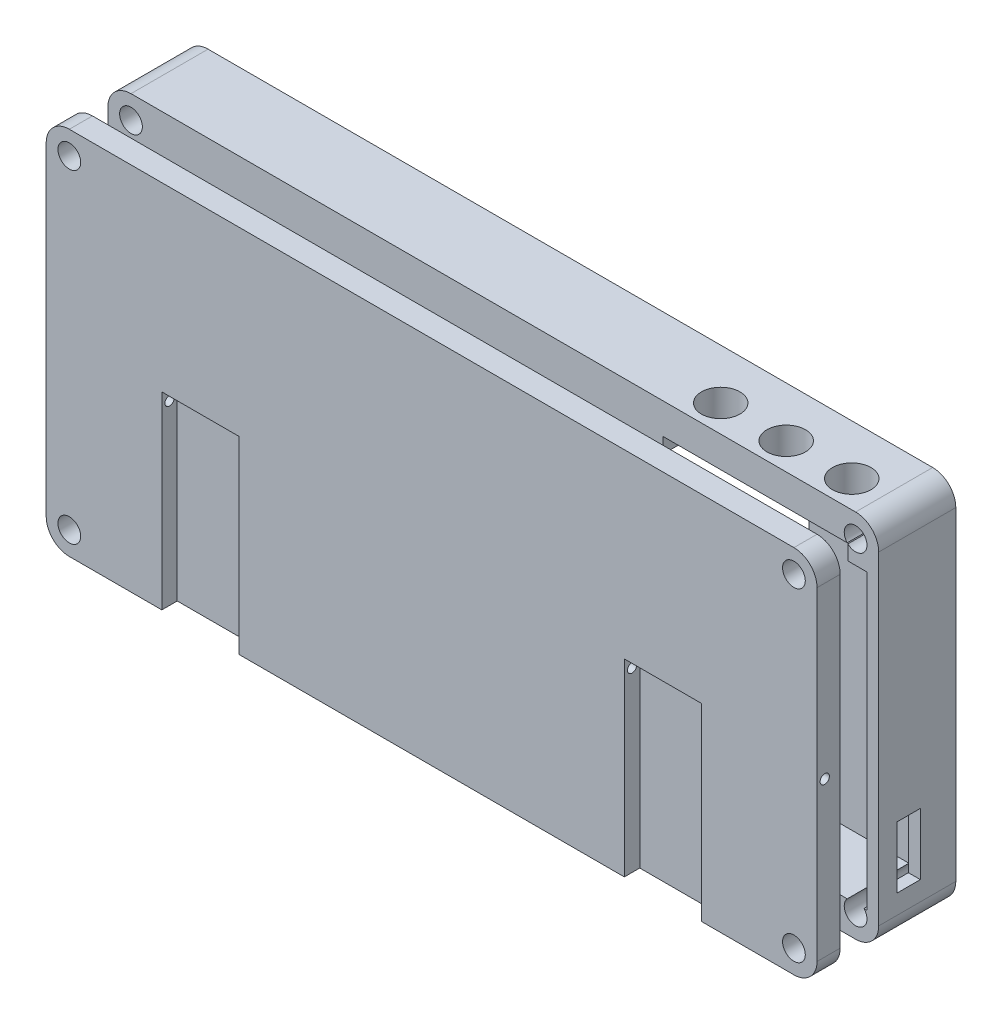
SolidWorks part; units mm, degrees
ref_plane "前视" through (0, 0, 0) normal (0, 0, 1) x (1, 0, 0)
ref_plane "上视" through (0, 0, 0) normal (0, 1, 0) x (1, 0, 0)
ref_plane "右视" through (0, 0, 0) normal (1, 0, 0) x (0, 0, -1)
sketch "草图1" plane through (0, 0, 0) normal (1, 0, 0) x (0, 0, -1)
  line L0 (0, 0) -> (10, 0)
  line L1 (0, 48) -> (0, 0)
  line L2 (10, 0) -> (10, 48)
  line L3 (10, 48) -> (0, 48)
  dimension "D1" = 10
  dimension "D2" = 48
extrude "凸台-拉伸2" add sketch "草图1" along normal blind 100 contours L1 L0 L2 L3
sketch "草图4" plane through (0, 0, 0) normal (0, 0, 1) x (1, 0, 0)
  line L0 (50, 0) -> (50, 46) construction
  line L1 (100, 0) -> (0, 0) construction
  line L2 (100, 48) -> (0, 48) construction
  line L3 (100, 48) -> (100, 0) construction
  line L4 (1.55, 42) -> (98.45, 42)
  line L5 (1.55, 42) -> (1.55, 4)
  line L6 (1.55, 4) -> (98.45, 4)
  line L7 (98.45, 42) -> (98.45, 4)
  line L8 (1.55, 42) -> (98.45, 4) construction
  line L9 (1.55, 4) -> (98.45, 42) construction
  line L10 (81.945, 37.525) -> (82.945, 36.525)
  line L11 (18.055, 37.525) -> (81.945, 37.525)
  line L12 (17.055, 36.525) -> (17.055, 10.475)
  line L13 (18.055, 9.475) -> (81.945, 9.475)
  line L14 (82.945, 36.525) -> (82.945, 10.475)
  line L15 (17.055, 37.525) -> (82.945, 9.475) construction
  line L16 (17.055, 9.475) -> (82.945, 37.525) construction
  line L17 (17.055, 36.525) -> (18.055, 37.525)
  line L18 (17.055, 10.475) -> (18.055, 9.475)
  line L19 (81.945, 9.475) -> (82.945, 10.475)
  point P6 (50, 23)
  point P13 (50, 23.5)
  dimension "D2" = 38
  dimension "D3" = 96.9
  dimension "D4" = 1.55
  dimension "D6" = 65.89
  dimension "D7" = 28.05
  dimension "D8" = 2
extrude "切除-拉伸3" cut sketch "草图4" against normal through all contours L14 L11 L12 L13 region at (50, 23.5, 0)
extrude "切除-拉伸4" cut sketch "草图4<3>" against normal offset from surface (8 mm away) 2 contours L7 L4 L5 L6 L11 L14 L13 L12 region at (50, 40.9592, 0) up to face at (50, 23.5, -10)
sketch "草图4<3>" plane through (0, 0, 0) normal (0, 0, 1) x (1, 0, 0) same geometry as "草图4"
chamfer "倒角4" distance 2 angle 60 8 edges at (17.055, 23.5, -10) (17.555, 37.025, -10) (50, 37.525, -10) (82.445, 37.025, -10) (82.945, 23.5, -10) (82.445, 9.975, -10) (50, 9.475, -10) (17.555, 9.975, -10) first distance on face at (17.055, 23.5, -9) first distance on face at (17.555, 37.025, -9) first distance on face at (50, 37.525, -9) first distance on face at (82.445, 37.025, -9) first distance on face at (82.945, 23.5, -9) first distance on face at (82.445, 9.975, -9) first distance on face at (50, 9.475, -9) first distance on face at (17.555, 9.975, -9)
fillet "圆角1" radius 3 4 edges at (0, 0, -5) (100, 0, -5) (0, 48, -5) (100, 48, -5)
sketch "草图13" plane through (0, 0, 0) normal (0, 0, 1) x (1, 0, 0)
  line L0 (1.55, 42) -> (98.45, 42) construction
  line L1 (96, 42) -> (72, 42)
  line L2 (96, 42) -> (96, 44)
  line L3 (96, 44) -> (72, 44)
  line L4 (72, 42) -> (72, 44)
  line L5 (100, 45) -> (100, 3) construction
  dimension "D1" = 4
  dimension "D2" = 28
  dimension "D3" = 2
extrude "切除-拉伸17" cut sketch "草图13" against normal up to surface (8 mm away) up to face at (50, 23, -8)
sketch "草图12" plane through (0, 48, 0) normal (0, 1, 0) x (1, 0, 0)
  line L1 (97, 10) -> (3, 10) construction
  line L3 (93, 3.5) -> (58.4452, 3.5) construction
  line L9 (100, 10) -> (100, 0) construction
  circle A0 centre (76, 3.5) radius 2.5
  circle A1 centre (93, 3.5) radius 2.5
  circle A2 centre (84.5, 3.5) radius 2.5
  dimension "D1" = 5
  dimension "D2" = 24
  dimension "D6" = 7
  dimension "D4" = 5
  dimension "D5" = 5
  dimension "D7" = 15.5
  dimension "D8" = 6.5
extrude "切除-拉伸18" cut sketch "草图12" against normal up to next contours A1 | L3 A2 | A2 L3 | L3 A0 | A0 L3 region at (76, 48, -2.439) region at (76, 48, -4.561) region at (84.5, 48, -2.439) region at (84.5, 48, -4.561) region at (93, 48, -5.9293)
sketch "草图15" plane through (0, 0, 0) normal (0, -1, 0) x (1, 0, 0)
  line L1 (68.5, -7) -> (72.5, -7)
  line L2 (68.5, -7) -> (68.5, -3)
  line L3 (68.5, -3) -> (72.5, -3)
  line L4 (72.5, -7) -> (72.5, -3)
  line L5 (100, 0) -> (100, -10) construction
  line L6 (97, -5) -> (89.4882, -5) construction
  line L7 (97, -10) -> (97, 0) construction
  arc A0 (68.5, -3) -> (68.5, -7) centre (68.5, -5) ccw
  arc A1 (72.5, -3) -> (72.5, -7) centre (72.5, -5) cw
  dimension "D1" = 27.5
  dimension "D2" = 31.5
  dimension "D3" = 4
sketch "草图14" plane through (100, 0, 0) normal (1, 0, 0) x (0, 0, -1)
  line L0 (10, 0) -> (0, 0) construction
  line L1 (2.4, 5.5) -> (5.4, 5.5)
  line L2 (2.4, 5.5) -> (2.4, 13.5)
  line L3 (2.4, 13.5) -> (5.4, 13.5)
  line L4 (5.4, 5.5) -> (5.4, 13.5)
  line L5 (8, 4) -> (8, 42) construction
  point P6 (3.9, 5.5)
  point P9 (8, 23)
  dimension "D1" = 8
  dimension "D2" = 3
  dimension "D3" = 5.5
  dimension "D4" = 2.6
extrude "切除-拉伸19" cut sketch "草图14" against normal up to next
extrude "切除-拉伸20" cut sketch "草图15" against normal up to next contours L1 L4 L3 L2 | A1 L4 | L2 A0 region at (70.5, 0, -5) region at (67.6512, 0, -5) region at (73.3488, 0, -5)
sketch "草图16" plane through (0, 0, 0) normal (0, 0, 1) x (1, 0, 0)
  line L0 (1.55, 4) -> (98.45, 4) construction
  line L1 (63.5, 4) -> (77.5, 4)
  line L2 (63.5, 4) -> (63.5, 2)
  line L3 (63.5, 2) -> (77.5, 2)
  line L4 (77.5, 4) -> (77.5, 2)
  line L8 (74.5, 0) -> (74.5, 4) construction
  line L9 (66.5, 4) -> (66.5, 0) construction
  dimension "D1" = 2
  dimension "D2" = 3
  dimension "D3" = 3
extrude "切除-拉伸21" cut sketch "草图16" against normal up to surface (8 mm away) up to face at (67, 33, -8)
sketch "草图7" plane through (0, 0, 0) normal (0, 0, 1) x (1, 0, 0)
  line L4 (0, 45) -> (0, 3)
  line L5 (3, 0) -> (97, 0)
  line L6 (3, 0) -> (97, 0)
  line L7 (100, 3) -> (100, 45)
  line L8 (0, 45) -> (0, 3)
  line L9 (100, 3) -> (100, 45)
  line L10 (97, 48) -> (3, 48)
  line L11 (97, 48) -> (3, 48)
  arc A4 (0, 3) -> (3, 0) centre (3, 3) ccw
  arc A5 (97, 0) -> (100, 3) centre (97, 3) ccw
  arc A6 (97, 0) -> (100, 3) centre (97, 3) ccw
  arc A7 (3, 48) -> (0, 45) centre (3, 45) ccw
  arc A8 (0, 3) -> (3, 0) centre (3, 3) ccw
  arc A9 (100, 45) -> (97, 48) centre (97, 45) ccw
  arc A10 (100, 45) -> (97, 48) centre (97, 45) ccw
  arc A11 (3, 48) -> (0, 45) centre (3, 45) ccw
  dimension "D1" = 0
extrude "凸台-拉伸3" add sketch "草图7" along normal blind 3 from offset 5 separate body
sketch "草图8" plane through (0, 0, 8) normal (0, 0, 1) x (1, 0, 0)
  line L0 (50, 48) -> (50, 0) construction
  line L1 (3, 0) -> (97, 0)
  line L2 (15, 0) -> (15, 24)
  line L3 (75, 0) -> (85, 0)
  line L4 (0, 45) -> (0, 3)
  line L5 (3, 0) -> (97, 0)
  line L6 (100, 3) -> (100, 45)
  line L7 (100, 3) -> (100, 45)
  line L8 (0, 45) -> (0, 3)
  line L9 (75, 0) -> (75, 24)
  line L10 (97, 48) -> (3, 48)
  line L11 (97, 48) -> (3, 48)
  line L12 (75, 24) -> (85, 24)
  line L13 (85, 0) -> (85, 24)
  line L14 (25, 0) -> (25, 24)
  line L15 (25, 24) -> (15, 24)
  line L17 (15, 24) -> (25, 24)
  line L18 (15, 24) -> (15, 24.5)
  line L19 (15, 24.5) -> (25, 24.5)
  line L20 (25, 24) -> (25, 24.5)
  line L21 (75, 24) -> (85, 24)
  line L22 (75, 24) -> (75, 24.5)
  line L23 (75, 24.5) -> (85, 24.5)
  line L24 (85, 24) -> (85, 24.5)
  arc A4 (3, 48) -> (0, 45) centre (3, 45) ccw
  arc A5 (0, 3) -> (3, 0) centre (3, 3) ccw
  arc A6 (97, 0) -> (100, 3) centre (97, 3) ccw
  arc A7 (97, 0) -> (100, 3) centre (97, 3) ccw
  arc A8 (3, 48) -> (0, 45) centre (3, 45) ccw
  arc A9 (0, 3) -> (3, 0) centre (3, 3) ccw
  arc A10 (100, 45) -> (97, 48) centre (97, 45) ccw
  arc A11 (100, 45) -> (97, 48) centre (97, 45) ccw
  line M13 (3, 0) -> (97, 0)
  dimension "D2" = 10
  dimension "D3" = 24
  dimension "D4" = 50
  dimension "D5" = 0.5
  dimension "D6" = 0.5
  dimension "D1" = 0
extrude "切除-拉伸9" cut sketch "草图8" against normal blind 2 contours L14 L15 L2 L1 | L13 L12 L9 M13 region at (20, 12, 8) region at (80, 12, 8)
sketch "草图9" plane through (75, 0, 0) normal (1, 0, 0) x (0, 0, -1)
  line L0 (-6, 24) -> (-8, 24) construction
  line L1 (-7, 24) -> (-7, 22.9259) construction
  circle A0 centre (-7, 23) radius 0.6
  dimension "D1" = 1
extrude "切除-拉伸10" cut sketch "草图9" against normal through all both and the other way through all
sketch "草图10" plane through (0, 0, 8) normal (0, 0, 1) x (1, 0, 0)
  line L0 (0, 24) -> (78.5549, 24) construction
  line L1 (0, 45) -> (0, 3) construction
  line L2 (50, 48) -> (50, 3.3947) construction
  line L3 (97, 48) -> (3, 48) construction
  circle A0 centre (3, 45) radius 1.475
  arc A1 (3, 48) -> (0, 45) centre (3, 45) ccw construction
  circle A3 centre (97, 45) radius 1.475
  circle A4 centre (97, 3) radius 1.475
  circle A5 centre (3, 3) radius 1.475
  dimension "D1" = 2.95
extrude "切除-拉伸12" cut sketch "草图10" against normal through all
extrude "切除-拉伸16" cut sketch "草图8<4>" against normal blind 1 contours L15 L20 L19 L18 | L12 L24 L23 L22 region at (20, 24.25, 8) region at (80, 24.25, 8)
sketch "草图8<4>" plane through (0, 0, 8) normal (0, 0, 1) x (1, 0, 0) same geometry as "草图8"
